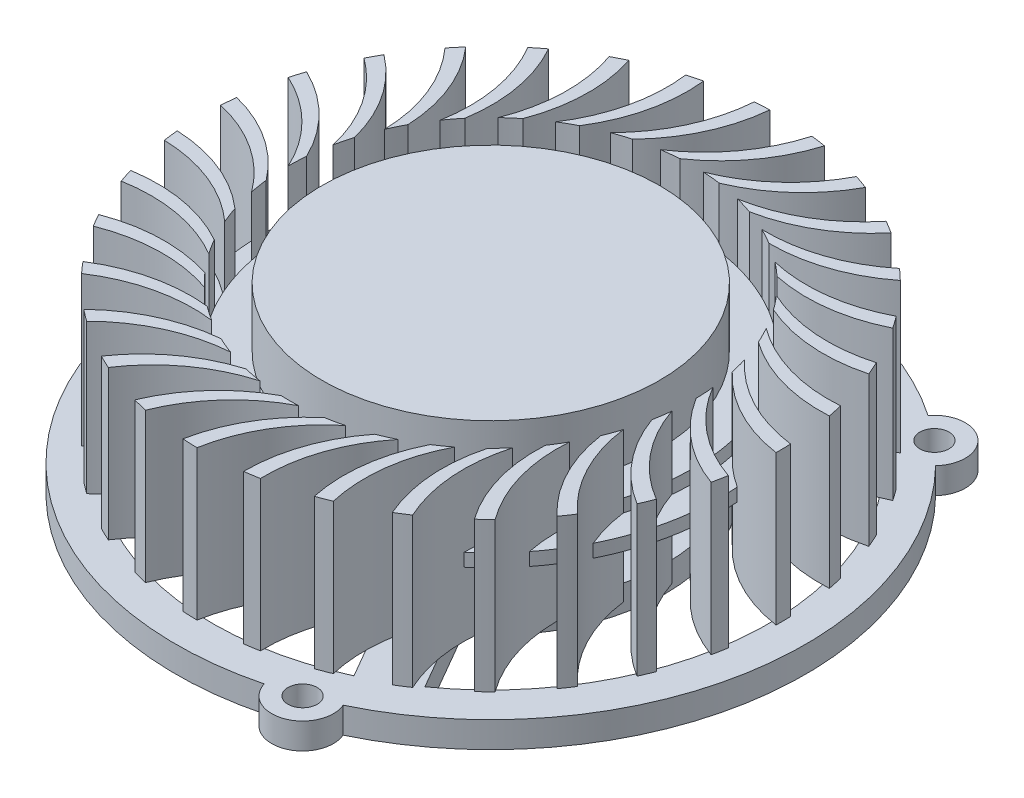
SolidWorks part; units mm, degrees
ref_plane "Front Plane" through (0, 0, 0) normal (0, 0, 1) x (1, 0, 0)
ref_plane "Top Plane" through (0, 0, 0) normal (0, 1, 0) x (1, 0, 0)
ref_plane "Right Plane" through (0, 0, 0) normal (1, 0, 0) x (0, 0, -1)
sketch "Sketch1" plane through (0, 0, 0) normal (0, 1, 0) x (1, 0, 0)
  line L0 (8.3823, 10.5185) -> (12.4446, 17.5546)
  line L1 (-13.3005, 2) -> (-21.425, 2)
  line L2 (-13.3005, 2) -> (-13.3005, -2) construction
  line L3 (-13.3005, -2) -> (-21.425, -2)
  line L4 (-21.425, 2) -> (-21.425, -2) construction
  line L5 (-17.3627, -2) -> (-17.3627, 2) construction
  line L6 (-13.3005, 0) -> (-21.425, 0) construction
  line L7 (4.9182, 12.5185) -> (8.9804, 19.5546)
  line L8 (4.9182, -12.5185) -> (8.9804, -19.5546)
  line L9 (8.3823, -10.5185) -> (12.4446, -17.5546)
  circle A0 centre (0, 0) radius 21.425
  circle A1 centre (0, 0) radius 13.45
  circle A2 centre (0, 0) radius 24.225
  point P9 (0, 0)
  point P10 (8.9804, 19.5546)
  point P22 (0, 0)
  point P89 (-17.3627, 0)
  dimension "D1" = 48.45
  dimension "D2" = 2.8
  dimension "D3" = 26.9
  dimension "D4" = 4
  dimension "D5" = 3
extrude "Boss-Extrude1" add sketch "Sketch1" against normal blind 2 contours A1 | A1 L0 A0 L7 | A2 A0 | A1 L8 A0 L9 | A1 L1 A0 L3 region at (8.6985, 0, -15.0662) region at (0, 0, 0) region at (8.6985, 0, 15.0662) region at (-17.397, 0, 0) region at (-23.5398, 0, 0)
sketch "Sketch2" plane through (0, 0, 0) normal (0, 0, 1) x (1, 0, 0)
  line L0 (0, 0) -> (0, 12)
  line L1 (0, 12) -> (13, 12)
  line L2 (13, 12) -> (13, 7.4434)
  line L3 (13, 7.4434) -> (15.6, 7.4434)
  line L4 (15.6, 7.4434) -> (15.6, 6.4434)
  line L5 (15.6, 6.4434) -> (22.3, 6.4434)
  line L6 (22.3, 6.4434) -> (22.3, 5.4434)
  line L7 (22.3, 5.4434) -> (10, 5.4434)
  line L8 (10, 5.4434) -> (10, 0)
  line L9 (24.225, 0) -> (-24.225, 0) construction
  line L10 (10, 0) -> (0, 0)
  line L11 (-24.225, -2) -> (24.225, -2) construction
  dimension "D1" = 13
  dimension "D2" = 22.3
  dimension "D3" = 15.6
  dimension "D5" = 14
  dimension "D6" = 2
  dimension "D7" = 10
  dimension "D8" = 1
revolve "Revolve1" add sketch "Sketch2" angle 360 about L0
sketch "Sketch3" plane through (0, 0, 0) normal (0, 1, 0) x (1, 0, 0)
  line L0 (-23.8803, 4.2107) -> (0, 0) construction
  line L1 (15.5868, 18.5756) -> (0, 0) construction
  line L2 (8.2935, -22.7863) -> (0, 0) construction
  circle A0 centre (-23.8803, 4.2107) radius 1.125
  circle A1 centre (15.5868, 18.5756) radius 1.125
  circle A2 centre (8.2935, -22.7863) radius 1.125
  circle A3 centre (-23.8803, 4.2107) radius 2.375
  circle A4 centre (8.2935, -22.7863) radius 2.375
  circle A5 centre (15.5868, 18.5756) radius 2.375
  point P5 (0, 0)
  point P10 (0, 0)
  point P16 (-23.8705, 4.1292)
  circle M16 centre (0, 0) radius 24.225
  dimension "D1" = 3
  dimension "D3" = 2.25
  dimension "D2" = 42
  dimension "D5" = 10
  dimension "D4" = 1.25
extrude "Boss-Extrude2" add sketch "Sketch3" against normal blind 2
extrude "Cut-Extrude1" cut sketch "Sketch3<2>" against normal blind 2 contours A0 M16 | A0 M16 | A1 | A2 region at (-23.3928, 0, -4.1248) region at (-24.3333, 0, -4.2906)
sketch "Sketch3<2>" plane through (0, 0, 0) normal (0, 1, 0) x (1, 0, 0) same geometry as "Sketch3"
sketch "Sketch4" plane through (0, 12, 0) normal (0, 1, 0) x (1, 0, 0)
  line L0 (-21.1761, 6.9903) -> (-15.541, 1.3552) construction
  line L1 (-21.5042, 5.9042) -> (-15.6, 0) construction
  arc A0 (-21.1761, 6.9903) -> (-15.541, 1.3552) centre (-26.3624, -3.8311) cw
  circle A1 centre (0, 0) radius 22.3 construction
  circle A2 centre (0, 0) radius 15.6 construction
  arc A3 (-21.5042, 5.9042) -> (-15.6, 0) centre (-26.5073, -5.0031) cw
  circle A4 centre (0, 0) radius 15.6 construction
  arc A5 (-21.1761, 6.9903) -> (-21.5042, 5.9042) centre (0, 0) ccw
  arc A6 (-15.541, 1.3552) -> (-15.6, 0) centre (0, 0) ccw
  point P10 (-21.5926, 5.572)
  point P13 (0, 0)
  point P17 (0, 0)
  dimension "D1" = 12
  dimension "D2" = 1
  dimension "D3" = 45
extrude "Boss-Extrude3" add sketch "Sketch4" against normal blind 11.5
sketch "Sketch5" plane through (0, 6.4434, 0) normal (0, 1, 0) x (1, 0, 0)
  circle A0 centre (0, 0) radius 17.6
  arc A4 (-15.541, 1.3552) -> (-21.1761, 6.9903) centre (-26.3624, -3.8311) ccw
  arc A5 (-15.6, 0) -> (-15.541, 1.3552) centre (0, 0) ccw
  arc A6 (-15.6, 0) -> (-21.5042, 5.9042) centre (-26.5073, -5.0031) ccw
  arc A7 (-21.5042, 5.9042) -> (-21.1761, 6.9903) centre (0, 0) ccw
  arc A8 (-15.541, 1.3552) -> (-21.1761, 6.9903) centre (-26.3624, -3.8311) ccw
  arc A9 (-15.6, 0) -> (-15.541, 1.3552) centre (0, 0) ccw
  arc A10 (-15.6, 0) -> (-21.5042, 5.9042) centre (-26.5073, -5.0031) ccw
  arc A11 (-21.5042, 5.9042) -> (-21.1761, 6.9903) centre (0, 0) ccw
  arc M5 (-21.1761, 6.9903) -> (-15.541, 1.3552) centre (-26.3624, -3.8311) cw
  arc M7 (-15.6, 0) -> (-21.5042, 5.9042) centre (-26.5073, -5.0031) ccw
  arc M8 (-21.5042, 5.9042) -> (-21.1761, 6.9903) centre (0, 0) ccw
  dimension "D2" = 2
  dimension "D1" = 0
extrude "Cut-Extrude3" cut sketch "Sketch5" against normal blind 1.6 contours A0 M7 M8 M5 region at (2.0216, 6.4434, -18.1183)
pattern_circular "CirPattern2" count 31 over 360 about axis through (0, 0, 0) along (0, -1, 0) of "Boss-Extrude3"
